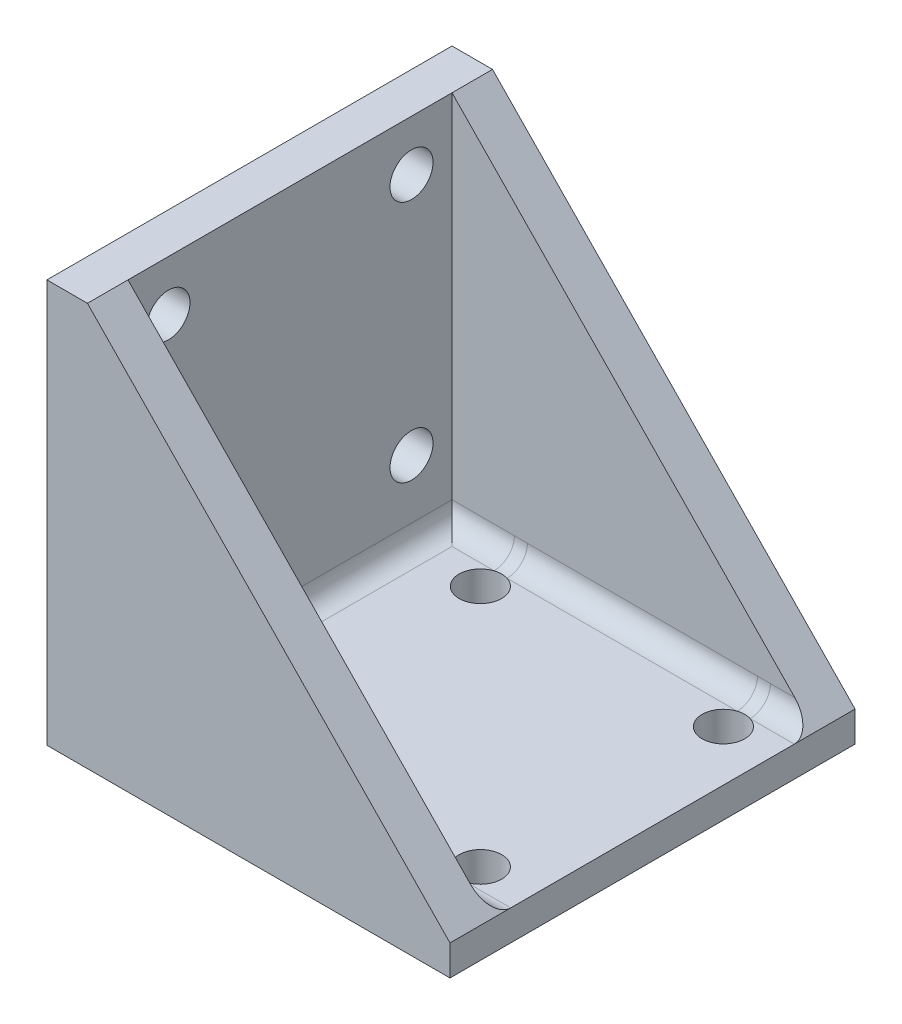
SolidWorks part; units mm, degrees
ref_plane "Front Plane" through (0, 0, 0) normal (0, 0, 1) x (1, 0, 0)
ref_plane "Top Plane" through (0, 0, 0) normal (0, 1, 0) x (1, 0, 0)
ref_plane "Right Plane" through (0, 0, 0) normal (1, 0, 0) x (0, 0, -1)
sketch "sss" plane through (0, 0, 0) normal (0, 1, 0) x (1, 0, 0)
  line L0 (-20.2, 0) -> (19.8, 0) construction
  line L1 (-20, -20) -> (19.8, -20)
  line L3 (-20, 20) -> (19.8, 20)
  line L4 (19.8, -20) -> (19.8, 20)
  line L5 (-19.9985, -20.2005) -> (19.8, 20) construction
  line L6 (-19.9985, 20.2005) -> (19.8, -20) construction
  line L7 (-0.1, 20) -> (-0.1, -20) construction
  line L8 (-20, 20) -> (-20, -20)
  circle A0 centre (-9.2, 12) radius 2.1
  circle A5 centre (14.8, 12) radius 2.1
  circle A6 centre (14.8, -12) radius 2.1
  circle A7 centre (-9.2, -12) radius 2.1
  point P0 (0, 0)
  dimension "D3" = 4.2
  dimension "D4" = 8
  dimension "D5" = 5
  dimension "D2" = 10.8
  dimension "D6" = 8
  dimension "D1" = 24
  dimension "D7" = 12
  dimension "D8" = 0
extrude "Boss-Extrude2" add sketch "sss" along normal blind 3
sketch "Sketch1" plane through (-20, 0, 0) normal (-1, 0, 0) x (0, 0, 1)
  line L0 (-20, 39.8) -> (20, 3) construction
  line L1 (-20, 0) -> (20, 0)
  line L2 (-20, 0) -> (-20, 39.8)
  line L3 (-20, 39.8) -> (20, 39.8)
  line L4 (20, 0) -> (20, 39.8)
  line L5 (20, 39.8) -> (-20, 3) construction
  line L6 (-20, 22.8) -> (20, 22.8) construction
  line L7 (0, 39.8) -> (0, 0) construction
  circle A1 centre (-12, 34.8) radius 2.125
  circle A2 centre (12, 34.8) radius 2.125
  circle A3 centre (12, 10.8) radius 2.125
  circle A4 centre (-12, 10.8) radius 2.125
  dimension "D2" = 4.25
  dimension "D1" = 12
  dimension "D3" = 5
  dimension "D4" = 8
  dimension "D5" = 10.8
extrude "Boss-Extrude3" add sketch "Sketch1" against normal blind 4
sketch "Sketch2" plane through (0, 0, 20) normal (0, 0, 1) x (1, 0, 0)
  line L0 (-20, 39.8) -> (-20, 0)
  line L1 (-20, 0) -> (19.8, 0) construction
  line L2 (-20, 39.8) -> (-20, 0) construction
  line L3 (-20, 0) -> (19.8, 0)
  line L4 (19.8, 0) -> (19.8, 3)
  line L5 (19.8, 3) -> (-16, 39.8)
  line L6 (-16, 39.8) -> (-20, 39.8)
extrude "Boss-Extrude4" add sketch "Sketch2" against normal blind 4
ref_plane "Plane1" through (0, 0, 0) normal (0, 0, 1) x (1, 0, 0)
mirror "Mirror1" about plane through (0, 0, 0) normal (0, 0, 1) of "Boss-Extrude4"
fillet "Fillet1" radius 2 3 edges at (1.9, 3, -16) (1.9, 3, 16) (-16, 3, 0)
equation "\"m4\"= 4.2"
equation "\"D3@sss\"=\"m4\""
